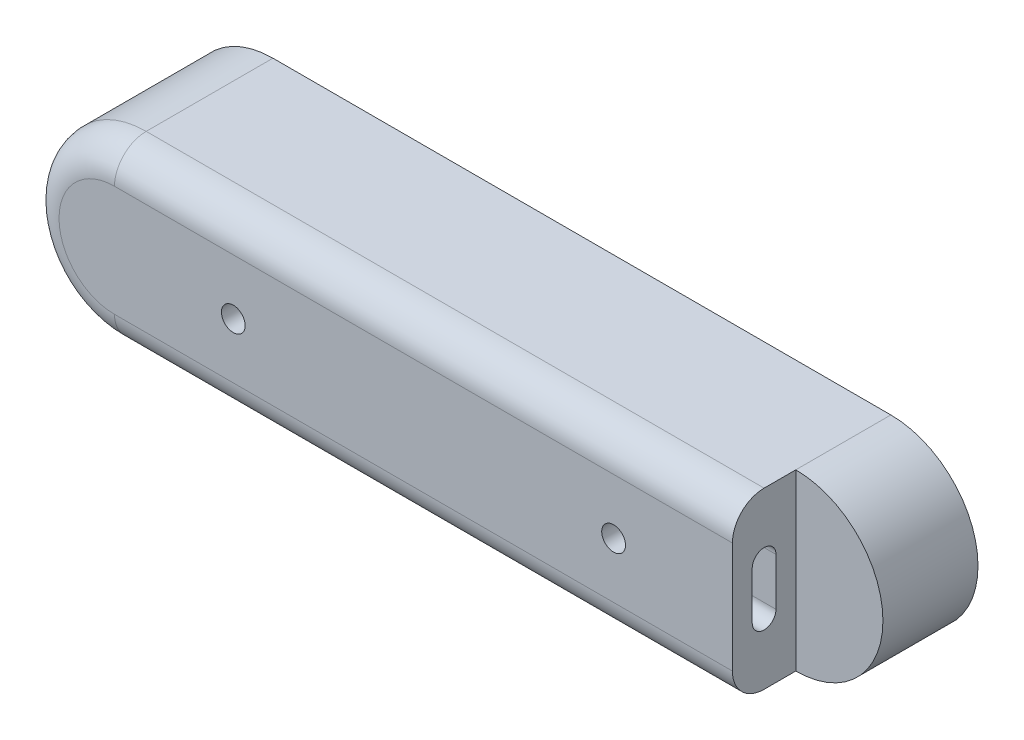
SolidWorks part; units mm, degrees
ref_plane "前视基准面" through (0, 0, 0) normal (0, 0, 1) x (1, 0, 0)
ref_plane "上视基准面" through (0, 0, 0) normal (0, 1, 0) x (1, 0, 0)
ref_plane "右视基准面" through (0, 0, 0) normal (1, 0, 0) x (0, 0, -1)
sketch "草图1" plane through (0, 0, 0) normal (0, 0, 1) x (1, 0, 0)
  line L0 (0, 0) -> (50000, 0) construction
  line L1 (0, 0) -> (0, 50000) construction
  line L3 (-50, 11) -> (50, 11)
  line L4 (-50, 11) -> (-50, -11)
  line L5 (-50, -11) -> (50, -11)
  line L6 (50, 11) -> (50, -11)
extrude "凸台-拉伸3" add sketch "草图1" along normal blind 20
sketch "草图3" plane through (0, 0, 20) normal (0, 0, 1) x (1, 0, 0)
  line L0 (-50, 11) -> (-50, -11) construction
  line L1 (-50, -11) -> (50, -11) construction
  line L2 (50, 11) -> (-50, 11) construction
  line L3 (0, 0) -> (0, 50000) construction
  line L4 (-39, 11) -> (39, 11)
  line L5 (-39, -11) -> (39, -11)
  circle A0 centre (-39, 0) radius 11
  circle A1 centre (39, 0) radius 11
  line M4 (-50, 11) -> (-50, -11)
  line M5 (-50, -11) -> (50, -11)
  line M6 (50, -11) -> (50, 11)
  line M7 (50, 11) -> (-50, 11)
extrude "切除-拉伸2" cut sketch "草图3" against normal blind 20 contours A0 M7 M4 | A0 M4 M5 | A1 M6 M5 | A1 M7 M6 region at (-47.543, 8.543, 20) region at (47.543, 8.543, 20) region at (-47.543, -8.543, 20) region at (47.543, -8.543, 20)
sketch "草图4" plane through (0, 0, 20) normal (0, 0, 1) x (1, 0, 0)
  line L0 (39, 11) -> (39, -11)
  circle A0 centre (39, 0) radius 11
  arc M4 (39, -11) -> (39, 11) centre (39, 0) ccw
extrude "切除-拉伸3" cut sketch "草图4" against normal blind 8 contours L0 M4 region at (43.6685, 0, 20)
sketch "草图5" plane through (39, 0, 0) normal (1, 0, 0) x (0, 0, -1)
  line L0 (-16, 11) -> (-16, 50011) construction
  line L1 (-12, 11) -> (-20, 11) construction
  line L2 (-20, 0) -> (49980, 0) construction
  line L3 (-20, 11) -> (-20, -11) construction
  line L5 (-17.5, 4.5) -> (-14.5, 4.5)
  line L6 (-17.5, 4.5) -> (-17.5, -4.5)
  line L7 (-17.5, -4.5) -> (-14.5, -4.5)
  line L8 (-14.5, 4.5) -> (-14.5, -4.5)
  point P4 (-16, 11)
  point P9 (-20, 0)
extrude "切除-拉伸5" cut sketch "草图5" against normal blind 7
sketch "草图7" plane through (32, 0, 0) normal (1, 0, 0) x (0, 0, -1)
  line L0 (-17.5, 0) -> (49982.5, 0) construction
  line L1 (-17.5, 4.5) -> (-17.5, -4.5) construction
  line L2 (-16, 4.5) -> (-16, 50004.5) construction
  line L3 (-14.5, 4.5) -> (-17.5, 4.5) construction
  line L4 (-14.5, 4.5) -> (-17.5, 4.5) construction
  line L5 (-14.5, -4.5) -> (-14.5, 4.5) construction
  line L6 (-16, 4.5) -> (-17.5, 4.5)
  line L7 (-17.5, 4.5) -> (-17.5, 3)
  line L8 (-16, 4.5) -> (-14.5, 4.5)
  line L9 (-14.5, 4.5) -> (-14.5, 3)
  line L10 (-17.5, -3) -> (-17.5, -4.5)
  line L11 (-17.5, -4.5) -> (-14.5, -4.5)
  line L12 (-14.5, -4.5) -> (-14.5, -3)
  circle A0 centre (-16, 3) radius 1.5
  circle A1 centre (-16, -3) radius 1.5
  point P4 (-17.5, 0)
  point P9 (-16, 4.5)
  line M4 (-17.5, 4.5) -> (-17.5, -4.5)
  line M5 (-17.5, -4.5) -> (-14.5, -4.5)
  line M6 (-14.5, -4.5) -> (-14.5, 4.5)
  line M7 (-14.5, 4.5) -> (-17.5, 4.5)
extrude "凸台-拉伸4" add sketch "草图7" along normal blind 7 contours A0 M7 M4 | A0 M6 M7 | A1 L11 M6 | A1 M5 M4 region at (32, 4.1649, 17.1649) region at (32, 4.1649, 14.8351) region at (32, -4.1649, 14.8351) region at (32, -4.1649, 17.1649)
sketch "草图8" plane through (0, -11, 0) normal (0, -1, 0) x (1, 0, 0)
  line L0 (0, 20) -> (0, 50020) construction
  line L1 (-39, 20) -> (39, 20) construction
  line L2 (-39, 10) -> (49961, 10) construction
  line L3 (-39, 0) -> (-39, 20) construction
  circle A0 centre (0, 10) radius 6
  point P4 (0, 20)
  point P9 (-39, 10)
extrude "切除-拉伸7" cut sketch "草图8" against normal blind 10
fillet "圆角1" radius 4 3 edges at (-50, 0, 20) (0, -11, 20) (0, 11, 20)
sketch "草图9" plane through (0, 0, 20) normal (0, 0, 1) x (1, 0, 0)
  line L0 (0, 0) -> (50000, 0) construction
  line L1 (0, 0) -> (0, 50000) construction
  circle A0 centre (-24, 0) radius 1.5
  arc A1 (-39, 7) -> (-39, -7) centre (-39, 0) ccw construction
  circle A2 centre (24, 0) radius 1.5
  dimension "D1" = 15
extrude "切除-拉伸8" cut sketch "草图9" against normal blind 5 contours A0 | A2
sketch "草图10" plane through (0, -11, 0) normal (0, -1, 0) x (1, 0, 0)
  circle A0 centre (0, 10) radius 6
extrude "凸台-拉伸5" add sketch "草图10" against normal blind 10
sketch "草图11" plane through (0, -11, 0) normal (0, -1, 0) x (1, 0, 0)
  line L0 (-39, 8) -> (49961, 8) construction
  line L1 (-39, 0) -> (-39, 16) construction
  line L2 (0, 0) -> (0, 50000) construction
  circle A0 centre (0, 8) radius 4
  point P4 (-39, 8)
extrude "切除-拉伸9" cut sketch "草图11" against normal blind 10
